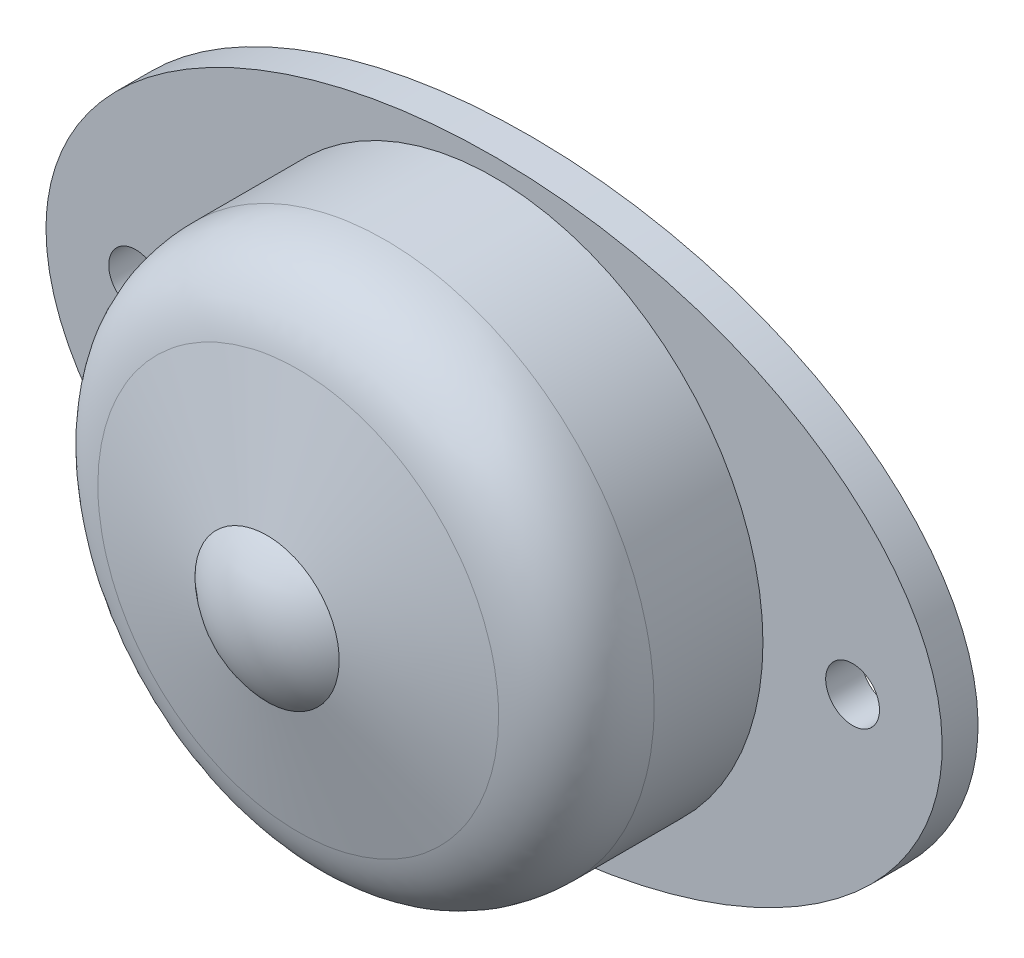
SolidWorks part; units mm, degrees
ref_plane "Front Plane" through (0, 0, 0) normal (0, 0, 1) x (1, 0, 0)
ref_plane "Top Plane" through (0, 0, 0) normal (0, 1, 0) x (1, 0, 0)
ref_plane "Right Plane" through (0, 0, 0) normal (1, 0, 0) x (0, 0, -1)
sketch "Sketch1" plane through (0, 0, 0) normal (0, 0, 1) x (1, 0, 0)
  line L0 (0, 26.4655) -> (0, -29.3966) construction
  line L1 (-20, 0) -> (20, 0) construction
  circle A0 centre (0, 0) radius 15
  circle A1 centre (0, 0) radius 7.5
  circle A2 centre (-20, 0) radius 1.5
  circle A3 centre (20, 0) radius 1.5
  ellipse E0 centre (0, 0) end of major axis (-25, 0) minor radius 16
  dimension "D3" = 30
  dimension "D4" = 15
  dimension "D7" = 3
  dimension "D8" = 3
  dimension "D1" = 50
  dimension "D2" = 32
  dimension "D5" = 20
  dimension "D6" = 20
extrude "Boss-Extrude6" add sketch "Sketch1" along normal blind 2 contours A0 | E0 | A2 | A3
extrude "Boss-Extrude7" add sketch "Sketch1<11>" along normal blind 12 contours A0 | A1
sketch "Sketch1<11>" plane through (0, 0, 0) normal (0, 0, 1) x (1, 0, 0) same geometry as "Sketch1"
sketch "Sketch5" plane through (0, 0, 0) normal (1, 0, 0) x (0, 0, -1)
  line L0 (0, 0) -> (-20.4312, 0) construction
  line L1 (-10.2156, 6) -> (-10.2156, -6)
  arc A0 (-10.2156, 6) -> (-10.2156, -6) centre (-10.2156, 0) ccw
  dimension "D1" = 6
  dimension "D2" = 10.2156
  dimension "D3" = 12
revolve "Revolve1" add sketch "Sketch5" angle 360 about L1
sketch "Sketch6" plane through (0, 0, 0) normal (1, 0, 0) x (0, 0, -1)
  line L0 (-12, 15) -> (-14.6663, 4.0238)
  line L1 (-14.6663, 4.0238) -> (-12, 7.5)
  line L2 (-12, 7.5) -> (-12, 15)
  line L3 (0, 0) -> (-19.0143, 0) construction
  circle A0 centre (-10.2156, 0) radius 6 construction
  dimension "D1" = 11.2954
revolve "Revolve2" add sketch "Sketch6" angle 360 about L3
fillet "Fillet1" radius 5 1 edges at (15, 0, 12) conic rho 0.5
